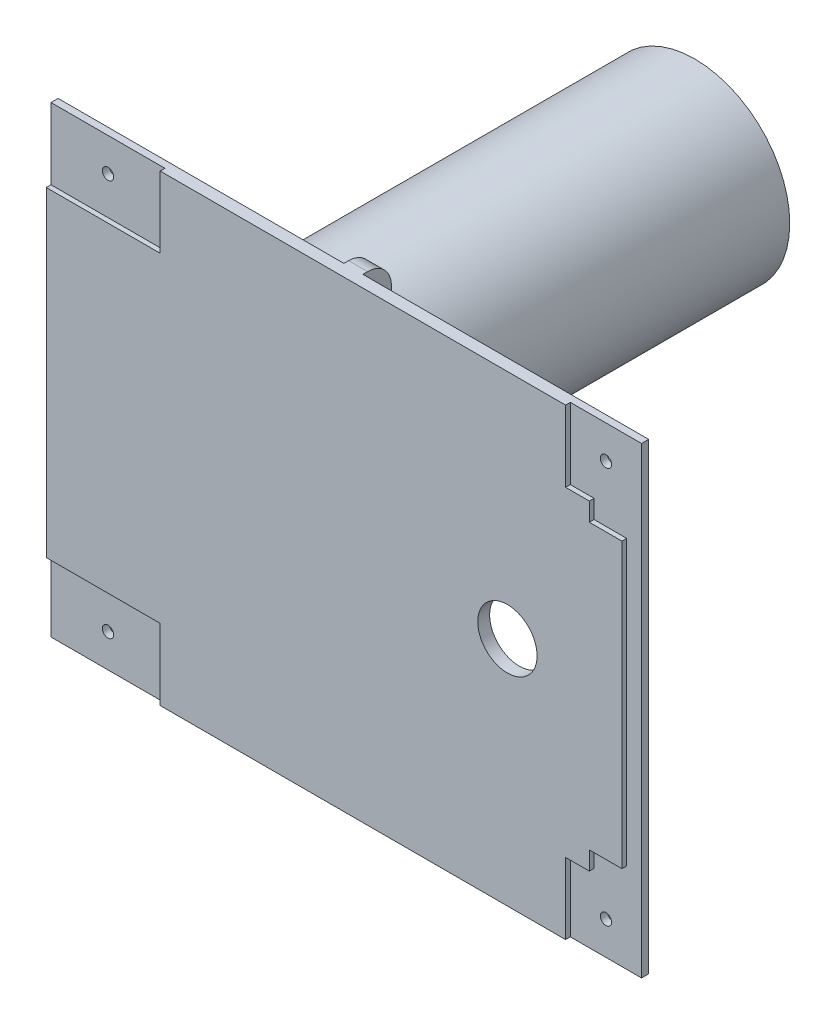
SolidWorks part; units mm, degrees
ref_plane "Alzado" through (0, 0, 0) normal (0, 0, 1) x (1, 0, 0)
ref_plane "Planta" through (0, 0, 0) normal (0, 1, 0) x (1, 0, 0)
ref_plane "Vista lateral" through (0, 0, 0) normal (1, 0, 0) x (0, 0, -1)
sketch "Croquis1" plane through (0, 0, 0) normal (0, 0, 1) x (1, 0, 0)
  line L1 (-117.2917, 97.7627) -> (131.4683, 97.7627)
  line L2 (-117.2917, 97.7627) -> (-117.2917, -97.2373)
  line L3 (-117.2917, -97.2373) -> (131.4683, -97.2373)
  line L4 (131.4683, 97.7627) -> (131.4683, -97.2373)
  dimension "D1" = 248.76
  dimension "D2" = 195
extrude "Saliente-Extruir1" add sketch "Croquis1" along normal blind 5
sketch "Croquis2" plane through (0, 0, 5) normal (0, 0, 1) x (1, 0, 0)
  line L0 (-117.2917, 0.2627) -> (131.4683, 0.2627) construction
  line L1 (-117.2917, 97.7627) -> (-117.2917, -97.2373) construction
  line L2 (131.4683, -97.2373) -> (131.4683, 97.7627) construction
  line L3 (-117.2917, -97.2373) -> (-69.2917, -97.2373)
  line L4 (-117.2917, -97.2373) -> (131.4683, -97.2373) construction
  line L5 (-69.2917, -97.2373) -> (-69.2917, -67.2373)
  line L6 (-69.2917, -67.2373) -> (-117.2917, -67.2373)
  line L7 (-117.2917, -67.2373) -> (-117.2917, -97.2373)
  line L8 (131.4683, 67.7627) -> (101.4683, 67.7627)
  line L9 (131.4683, -97.2373) -> (101.4683, -97.2373)
  line L10 (131.4683, -97.2373) -> (131.4683, -67.2373)
  line L11 (131.4683, -67.2373) -> (101.4683, -67.2373)
  line L12 (101.4683, -97.2373) -> (101.4683, -67.2373)
  line L13 (101.4683, 97.7627) -> (101.4683, 67.7627)
  line L14 (131.4683, 97.7627) -> (101.4683, 97.7627)
  line L15 (131.4683, 97.7627) -> (131.4683, 67.7627)
  line L16 (-69.2917, 67.7627) -> (-117.2917, 67.7627)
  line L17 (-69.2917, 97.7627) -> (-69.2917, 67.7627)
  line L18 (-117.2917, 97.7627) -> (-69.2917, 97.7627)
  line L19 (-117.2917, 67.7627) -> (-117.2917, 97.7627)
  dimension "D1" = 48
  dimension "D2" = 30
  dimension "D3" = 30
  dimension "D4" = 30
extrude "Cortar-Extruir1" cut sketch "Croquis2" against normal blind 2
sketch "Croquis3" plane through (0, 0, 5) normal (0, 0, 1) x (1, 0, 0)
  line L0 (-69.2917, 97.7627) -> (-117.2917, 97.7627) construction
  line L1 (116.4683, 83.7627) -> (116.4683, 67.7627) construction
  line L3 (116.4683, -83.2373) -> (116.4683, -67.2373) construction
  line L5 (131.4683, -67.2373) -> (101.4683, -67.2373) construction
  line L6 (101.4683, 67.7627) -> (131.4683, 67.7627) construction
  line L7 (-93.2917, 83.7627) -> (-93.2917, 67.7627) construction
  line L8 (-117.2917, 67.7627) -> (-69.2917, 67.7627) construction
  line L9 (-93.2917, -83.2373) -> (-93.2917, -67.2373) construction
  line L10 (-69.2917, -67.2373) -> (-117.2917, -67.2373) construction
  circle A0 centre (-93.2917, 83.7627) radius 2.375
  circle A1 centre (-93.2917, -83.2373) radius 2.375
  circle A2 centre (116.4683, 83.7627) radius 2.375
  circle A3 centre (116.4683, -83.2373) radius 2.375
  dimension "D2" = 4.75
  dimension "D3" = 4.75
  dimension "D5" = 4.75
  dimension "D6" = 4.75
  dimension "D1" = 14
  dimension "D4" = 14
  dimension "D7" = 209.76
  dimension "D8" = 16
  dimension "D9" = 16
extrude "Cortar-Extruir2" cut sketch "Croquis3" against normal blind 10
sketch "Croquis4" plane through (0, 0, 0) normal (0, 0, -1) x (-1, 0, 0)
  line L7 (-131.4683, 97.7627) -> (117.2917, 97.7627) construction
  line L9 (117.2917, 97.7627) -> (117.2917, -97.2373) construction
  circle A0 centre (55.1017, 0.2627) radius 40
  dimension "D3" = 80
  dimension "D1" = 62.19
  dimension "D2" = 97.5
extrude "Saliente-Extruir2" add sketch "Croquis4" along normal blind 206 contours A0
sketch "Croquis5" plane through (0, 0, 0) normal (0, 0, -1) x (-1, 0, 0)
  line L0 (-131.4683, 0.2627) -> (117.2917, 0.2627) construction
  line L1 (-131.4683, -97.2373) -> (-131.4683, 97.7627) construction
  line L2 (117.2917, 97.7627) -> (117.2917, -97.2373) construction
  circle A0 centre (-76.9683, 0.2627) radius 12.5
  dimension "D1" = 25
  dimension "D2" = 54.5
extrude "Cortar-Extruir3" cut sketch "Croquis5" against normal blind 10
sketch "Croquis6" plane through (0, 0, 0) normal (0, 0, -1) x (-1, 0, 0)
  line L0 (-131.4683, 97.7627) -> (117.2917, 97.7627) construction
  line L1 (-7.0883, 97.7627) -> (-7.0883, -97.2373)
  line L2 (117.2917, -97.2373) -> (-131.4683, -97.2373) construction
  line L3 (-7.0883, 97.7627) -> (117.2917, 97.7627)
  line L4 (117.2917, 97.7627) -> (117.2917, -97.2373)
  line L5 (117.2917, -97.2373) -> (-7.0883, -97.2373)
  line L6 (-131.4683, 0.2627) -> (56.0317, 0.2627)
  line L7 (-131.4683, -97.2373) -> (-131.4683, 97.7627) construction
  circle A1 centre (56.0317, 0.2627) radius 100
  dimension "D1" = 200
  dimension "D2" = 187.5
sketch "Croquis9" plane through (0, 97.7627, 0) normal (0, 1, 0) x (1, 0, 0)
  line L0 (7.0883, 0) -> (7.0883, -5)
  line L1 (131.4683, 0) -> (-117.2917, 0) construction
  line L2 (101.4683, -5) -> (-69.2917, -5) construction
ref_plane "Plano3" through (7.0883, 0, 0) normal (1, 0, 0) x (0, 0, -1)
sketch "Croquis12" plane through (7.0883, 0, 0) normal (1, 0, 0) x (0, 0, -1)
  line L0 (0, 97.7627) -> (0, 67.7627)
  line L1 (0, 67.7627) -> (12, 67.7627)
  line L2 (12, 67.7627) -> (12, 97.7627)
  line L3 (12, 97.7627) -> (0, 97.7627)
  line L4 (0, -97.2373) -> (12, -97.2373)
  line L5 (12, -97.2373) -> (12, -67.2373)
  line L6 (12, -67.2373) -> (0, -67.2373)
  line L7 (0, -67.2373) -> (0, -97.2373)
  dimension "D1" = 30
  dimension "D2" = 12
  dimension "D3" = 30
  dimension "D4" = 12
extrude "Saliente-Extruir3" add sketch "Croquis12" along normal mid plane 8
fillet "Redondeo1" radius 10 2 edges at (7.0883, -67.2373, 0) (7.0883, 67.7627, 0)
fillet "Redondeo2" radius 10 2 edges at (7.0883, 67.7627, -12) (7.0883, -67.2373, -12)
fillet "Redondeo3" radius 10 2 edges at (7.0883, -97.2373, -12) (7.0883, 97.7627, -12)
sketch "Croquis13" plane through (11.0883, 0, 0) normal (1, 0, 0) x (0, 0, -1)
  line L0 (-5, 0.2627) -> (206, 0.2627) construction
  line L1 (-5, -67.2373) -> (-5, 67.7627) construction
  line L2 (206, -39.7373) -> (206, 40.2627) construction
  line L3 (6, 87.7627) -> (12, 87.7627) construction
  line L4 (6, 87.7627) -> (6, 77.7627) construction
  circle A0 centre (6, 87.7627) radius 1.625
  circle A1 centre (6, 77.7627) radius 1.625
  circle A2 centre (6, -77.2373) radius 1.625
  circle A3 centre (6, -87.2373) radius 1.625
  dimension "D3" = 3.25
  dimension "D4" = 3.25
  dimension "D1" = 6
extrude "Cortar-Extruir5" cut sketch "Croquis13" against normal through all both and the other way through all
sketch "Croquis14" plane through (0, 0, 0) normal (0, 0, -1) x (-1, 0, 0)
  line L0 (-7.0883, 97.7627) -> (-7.0883, -97.2373)
  line L1 (-7.0883, 97.7627) -> (117.2917, 97.7627)
  line L2 (117.2917, 97.7627) -> (117.2917, -97.2373)
  line L3 (117.2917, -97.2373) -> (-7.0883, -97.2373)
sketch "Croquis15" plane through (0, 0, 5) normal (0, 0, 1) x (1, 0, 0)
  line L0 (111.4683, 67.7627) -> (131.4683, 67.7627)
  line L1 (111.4683, 67.7627) -> (111.4683, 60.0127)
  line L2 (131.4683, -67.2373) -> (101.4683, -67.2373) construction
  line L3 (111.4683, -67.2373) -> (111.4683, -59.4873)
  line L4 (111.4683, -59.4873) -> (125.2183, -59.4873)
  line L5 (125.2183, -59.4873) -> (125.2183, 60.0127)
  line L6 (111.4683, 60.0127) -> (125.2183, 60.0127)
  line L7 (111.4683, -67.2373) -> (131.4683, -67.2373)
  line L10 (131.4683, -67.2373) -> (131.4683, 67.7627)
  dimension "D1" = 119.5
  dimension "D2" = 7.75
  dimension "D3" = 13.75
extrude "Cortar-Extruir7" cut sketch "Croquis15" against normal blind 2
